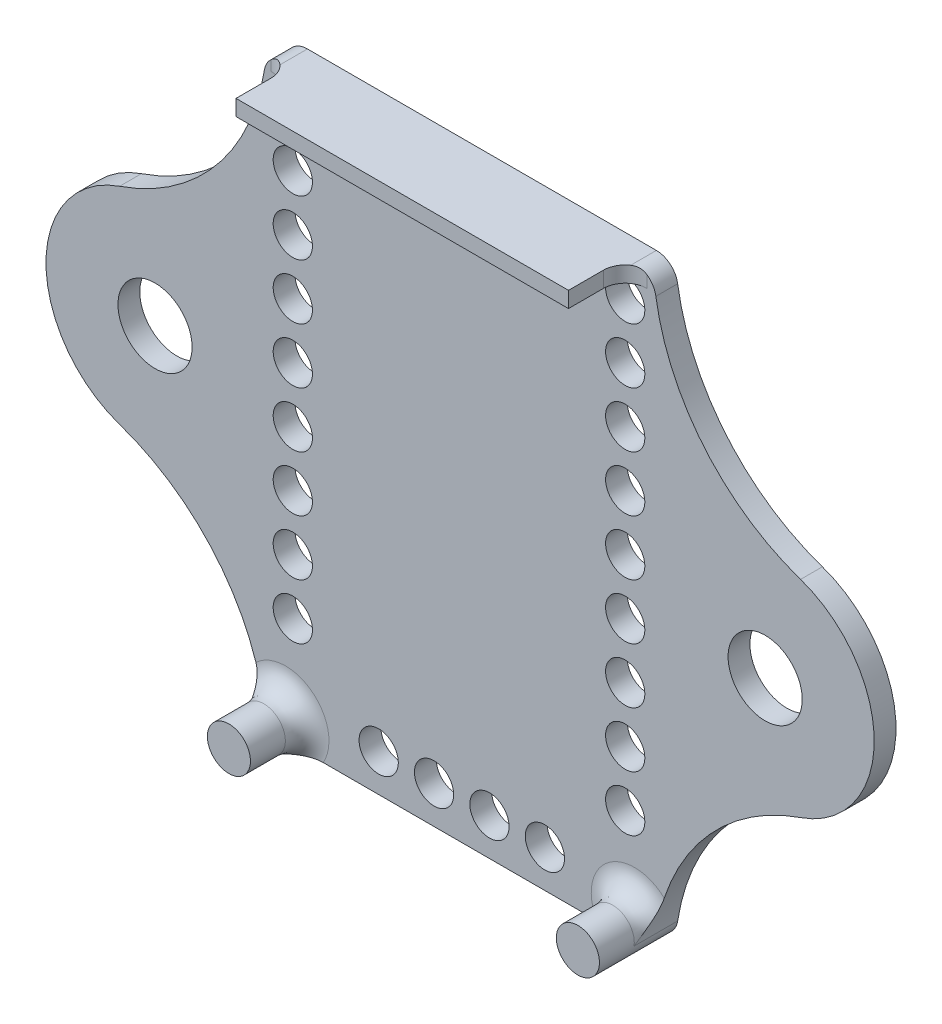
SolidWorks part; units mm, degrees
ref_plane "Front Plane" through (0, 0, 0) normal (0, 0, 1) x (1, 0, 0)
ref_plane "Top Plane" through (0, 0, 0) normal (0, 1, 0) x (1, 0, 0)
ref_plane "Right Plane" through (0, 0, 0) normal (1, 0, 0) x (0, 0, -1)
sketch "Sketch1" plane through (0, 0, 0) normal (0, 0, 1) x (1, 0, 0)
  line L0 (-35.001, -25.4128) -> (-19.001, -25.4128)
  line L1 (-18.0137, -26.4001) -> (-18.0137, -51.4001)
  line L2 (-19.001, -52.3874) -> (-35.001, -52.3874)
  line L3 (-35.9884, -51.4001) -> (-35.9884, -26.4001)
  line L4 (-35.9884, -38.9001) -> (-40.9884, -38.9001)
  line L5 (-18.0137, -38.9001) -> (-13.0137, -38.9001)
  line L6 (-40.9884, -33.9001) -> (-35.9884, -33.9001)
  line L7 (-40.9884, -43.9001) -> (-35.9884, -43.9001)
  line L8 (-13.0137, -43.9001) -> (-18.0137, -43.9001)
  line L9 (-13.0137, -33.9001) -> (-18.0137, -33.9001)
  circle A0 centre (-34.671, -27.0511) radius 0.5
  circle A1 centre (-34.671, -29.5911) radius 0.5
  circle A2 centre (-34.671, -32.1311) radius 0.5
  circle A3 centre (-34.671, -34.6711) radius 0.5
  circle A4 centre (-34.671, -37.2111) radius 0.5
  circle A5 centre (-34.671, -39.7511) radius 0.5
  circle A6 centre (-34.671, -42.2911) radius 0.5
  circle A7 centre (-34.671, -44.8311) radius 0.5
  circle A8 centre (-34.671, -47.3711) radius 0.5
  circle A9 centre (-30.7341, -50.6731) radius 0.55
  circle A10 centre (-28.1941, -50.6731) radius 0.55
  circle A11 centre (-25.6541, -50.6731) radius 0.55
  circle A12 centre (-23.114, -50.6731) radius 0.55
  circle A13 centre (-19.4311, -47.3711) radius 0.5
  circle A14 centre (-19.4311, -44.8311) radius 0.5
  circle A15 centre (-19.4311, -42.2911) radius 0.5
  circle A16 centre (-19.4311, -39.7511) radius 0.5
  circle A17 centre (-19.4311, -37.2111) radius 0.5
  circle A18 centre (-19.4311, -34.6711) radius 0.5
  circle A19 centre (-19.4311, -32.1311) radius 0.5
  circle A20 centre (-19.4311, -29.5911) radius 0.5
  circle A21 centre (-19.4311, -27.0511) radius 0.5
  circle A22 centre (-35.001, -26.4001) radius 0.9873
  circle A23 centre (-19.001, -26.4001) radius 0.9873
  circle A24 centre (-35.001, -51.4001) radius 0.9873
  circle A25 centre (-19.001, -51.4001) radius 0.9873
  circle A28 centre (-34.671, -27.0511) radius 0.9
  circle A29 centre (-34.671, -29.5911) radius 0.9
  circle A30 centre (-34.671, -32.1311) radius 0.9
  circle A31 centre (-34.671, -34.6711) radius 0.9
  circle A32 centre (-34.671, -37.2111) radius 0.9
  circle A33 centre (-34.671, -39.7511) radius 0.9
  circle A34 centre (-34.671, -42.2911) radius 0.9
  circle A35 centre (-34.671, -44.8311) radius 0.9
  circle A36 centre (-34.671, -47.3711) radius 0.9
  circle A37 centre (-30.7341, -50.6731) radius 0.9
  circle A38 centre (-28.1941, -50.6731) radius 0.9
  circle A39 centre (-25.6541, -50.6731) radius 0.9
  circle A40 centre (-23.114, -50.6731) radius 0.9
  circle A41 centre (-19.4311, -47.3711) radius 0.9
  circle A42 centre (-19.4311, -44.8311) radius 0.9
  circle A43 centre (-19.4311, -42.2911) radius 0.9
  circle A44 centre (-19.4311, -39.7511) radius 0.9
  circle A45 centre (-19.4311, -37.2111) radius 0.9
  circle A46 centre (-19.4311, -34.6711) radius 0.9
  circle A47 centre (-19.4311, -32.1311) radius 0.9
  circle A48 centre (-19.4311, -29.5911) radius 0.9
  circle A49 centre (-19.4311, -27.0511) radius 0.9
  circle A50 centre (-40.9884, -38.9001) radius 1.7
  circle A51 centre (-13.0137, -38.9001) radius 1.7
  circle A52 centre (-40.9884, -38.9001) radius 5
  circle A53 centre (-13.0137, -38.9001) radius 5
extrude "Boss-Extrude1" add sketch "Sketch1" along normal blind 1 contours A52 A50 | A53 A51 | A52 L7 L3 | A49 A23 L0 A22 A28 L3 A24 L2 A25 L1 A48 A47 A46 A45 A44 A43 A42 A41 A40 A39 A38 A37 A36 A35 A34 A33 | A53 L1 L8 | A53 L9 L1 | A52 L3 L6 | A28 A22 | A49 A23 | A25 | A24 region at (-26.9992, -38.717, 0) region at (-35.1699, -26.067, 0) region at (-18.8063, -26.1053, 0) region at (-37.1052, -35.0169, 0) region at (-16.8969, -35.0169, 0) region at (-37.5528, -42.3356, 0) region at (-37.1052, -42.7832, 0) region at (-16.8969, -42.7832, 0) region at (-16.4492, -35.4645, 0) region at (-35.001, -51.4001, 0) region at (-19.001, -51.4001, 0)
fillet "Fillet1" radius 10 4 edges at (-35.9884, -43.9001, 0.5) (-35.9884, -33.9001, 0.5) (-18.0137, -33.9001, 0.5) (-18.0137, -43.9001, 0.5)
sketch "Sketch2" plane through (0, 0, 1) normal (0, 0, 1) x (1, 0, 0)
  line L0 (-27.001, -25.4128) -> (-27.001, -26.1371)
  line L1 (-35.001, -25.4128) -> (-19.001, -25.4128) construction
  line L2 (-27.001, -26.1371) -> (-19.4311, -26.1371)
  line L3 (-19.4311, -26.1371) -> (-19.4311, -25.4128)
  line L4 (-27.001, -26.1371) -> (-34.6754, -26.1371)
  line L5 (-34.6754, -26.1371) -> (-34.6754, -25.4128)
  line L6 (-34.6754, -25.4128) -> (-19.4311, -25.4128)
  circle A0 centre (-35.001, -51.4001) radius 0.9873
  circle A1 centre (-19.001, -51.4001) radius 0.9873
  arc M6 (-35.9766, -51.5517) -> (-35.001, -52.3874) centre (-35.001, -51.4001) ccw
  arc M8 (-19.001, -52.3874) -> (-18.0254, -51.5517) centre (-19.001, -51.4001) ccw
  line M13 (-19.001, -25.4128) -> (-35.001, -25.4128)
extrude "Boss-Extrude2" add sketch "Sketch2" along normal blind 2.6 contours A1 M8 | A0 M6 | L2 L3 L0 M13 | L5 L4 L0 M13 region at (-23.216, -25.7749, 1) region at (-30.8382, -25.7749, 1) region at (-35.001, -51.4001, 1) region at (-19.001, -51.4001, 1)
fillet "Fillet2" radius 1 2 edges at (-19.4311, -25.7749, 1) (-34.6754, -25.7749, 1)
fillet "Fillet3" radius 1 2 edges at (-19.6433, -50.6503, 1) (-34.3588, -50.6503, 1)
